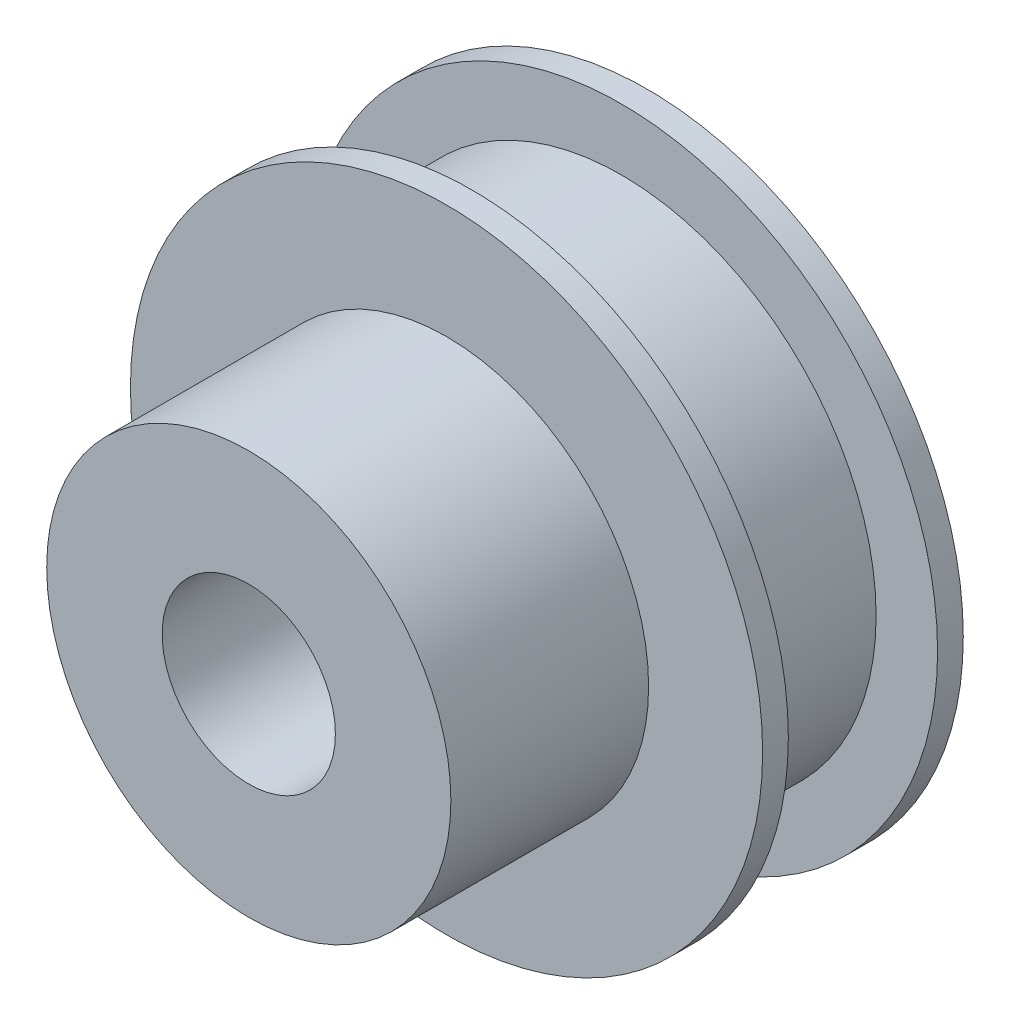
SolidWorks part; units mm, degrees
ref_plane "Front Plane" through (0, 0, 0) normal (0, 0, 1) x (1, 0, 0)
ref_plane "Top Plane" through (0, 0, 0) normal (0, 1, 0) x (1, 0, 0)
ref_plane "Right Plane" through (0, 0, 0) normal (1, 0, 0) x (0, 0, -1)
sketch "Sketch1" plane through (0, 0, 0) normal (1, 0, 0) x (0, 0, -1)
  line L0 (0, 0) -> (50000, 0) construction
  line L1 (0, 3.81) -> (17.526, 3.81)
  line L2 (17.526, 3.81) -> (17.526, 13.9065)
  line L3 (17.526, 13.9065) -> (16.3957, 13.9065)
  line L4 (16.3957, 13.9065) -> (16.3957, 11.2014)
  line L5 (16.3957, 11.2014) -> (9.8298, 11.2014)
  line L6 (9.8298, 11.2014) -> (9.8298, 13.9065)
  line L7 (9.8298, 13.9065) -> (8.6995, 13.9065)
  line L8 (8.6995, 13.9065) -> (8.6995, 8.89)
  line L9 (8.6995, 8.89) -> (0, 8.89)
  line L10 (0, 8.89) -> (0, 3.81)
  dimension "D1" = 3.81
  dimension "D2" = 8.89
  dimension "D3" = 13.9065
  dimension "D4" = 11.2014
  dimension "D5" = 17.526
  dimension "D6" = 6.5659
  dimension "D7" = 1.1303
  dimension "D8" = 1.1303
revolve "Revolve1" add sketch "Sketch1" angle 360 about L0
ref_axis "Axis1" through (0, 0, -17.526) along (0, 0, 1)
